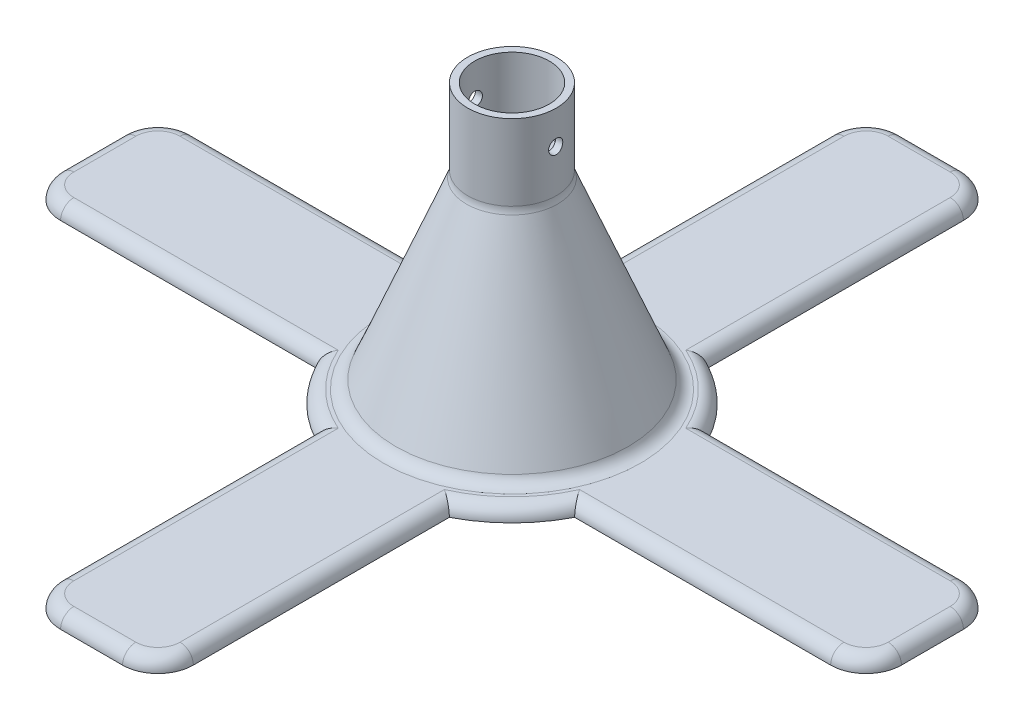
SolidWorks part; units mm, degrees
ref_plane "Front Plane" through (0, 0, 0) normal (0, 0, 1) x (1, 0, 0)
ref_plane "Top Plane" through (0, 0, 0) normal (0, 1, 0) x (1, 0, 0)
ref_plane "Right Plane" through (0, 0, 0) normal (1, 0, 0) x (0, 0, -1)
sketch "Sketch1" plane through (0, 0, 0) normal (0, 1, 0) x (1, 0, 0)
  line L0 (0, 95) -> (0, -95)
  line L1 (0, -55) -> (0, 55) construction
  line L2 (15, -29.159) -> (15, -95)
  line L3 (-95, 0) -> (95, 0)
  line L4 (-55, 0) -> (55, 0) construction
  line L5 (29.159, 15) -> (95, 15)
  line L6 (95, 15) -> (95, 0)
  line L7 (95, -15) -> (29.159, -15)
  line L8 (29.159, -15) -> (95, -15)
  line L9 (95, -15) -> (95, 0)
  line L10 (15, -95) -> (0, -95)
  line L11 (-15, -95) -> (0, -95)
  line L12 (-15, -95) -> (-15, -29.159)
  line L13 (-29.159, -15) -> (-95, -15)
  line L14 (-95, -15) -> (-95, 0)
  line L15 (-95, 15) -> (-95, 0)
  line L16 (-95, 15) -> (-29.159, 15)
  line L17 (-15, 29.159) -> (-15, 95)
  line L18 (-15, 95) -> (0, 95)
  line L19 (15, 95) -> (0, 95)
  line L20 (15, 95) -> (15, 29.159)
  circle A0 centre (0, 0) radius 32.791
  point P6 (0, 0)
  point P12 (0, 0)
  point P35 (0, 0)
  dimension "D3" = 30
  dimension "D1" = 190
  dimension "D2" = 190
  dimension "D4" = 15
  dimension "D5" = 4
extrude "Boss-Extrude1" add sketch "Sketch1" along normal blind 3 contours A0 L3 L6 L5 | A0 L7 L9 L3 | L0 A0 L3 | L3 A0 L0 | L0 A0 L3 | L3 A0 L0 | A0 L0 L18 L17 | A0 L20 L19 L0 | A0 L16 L15 L3 | A0 L3 L14 L13 | A0 L12 L11 L0 | A0 L0 L10 L2 region at (7.5708, 0, -63.2951) region at (-7.5708, 0, -63.2951) region at (13.9169, 0, -13.9169) region at (-13.9169, 0, -13.9169) region at (13.9169, 0, 13.9169) region at (-13.9169, 0, 13.9169) region at (7.5708, 0, 63.2951) region at (-7.5708, 0, 63.2951) region at (-63.2951, 0, 7.5708) region at (-63.2951, 0, -7.5708) region at (63.2951, 0, -7.5708) region at (63.2951, 0, 7.5708)
fillet "Fillet4" radius 8 8 edges at (15, 1.5, 95) (-15, 1.5, 95) (-95, 1.5, 15) (-95, 1.5, -15) (-15, 1.5, -95) (15, 1.5, -95) (95, 1.5, -15) (95, 1.5, 15)
fillet "Fillet5" radius 3 24 edges at (-12.6569, 3, 92.6569) (-15, 3, 58.0795) (-23.1867, 3, 23.1867) (-58.0795, 3, 15) (-92.6569, 3, 12.6569) (-95, 3, 0) (-92.6569, 3, -12.6569) (-58.0795, 3, -15) (-23.1867, 3, -23.1867) (-15, 3, -58.0795) (-12.6569, 3, -92.6569) (0, 3, -95) (12.6569, 3, -92.6569) (15, 3, -58.0795) (23.1867, 3, -23.1867) (58.0795, 3, -15) (92.6569, 3, -12.6569) (95, 3, 0) (92.6569, 3, 12.6569) (58.0795, 3, 15) (23.1867, 3, 23.1867) (15, 3, 58.0795) (12.6569, 3, 92.6569) (0, 3, 95)
sketch "Sketch4" plane through (0, 3, 0) normal (0, 1, 0) x (1, 0, 0)
  circle A0 centre (0, 0) radius 10
extrude "Boss-Extrude4" add sketch "Sketch4" along normal blind 60
chamfer "Chamfer2" distance 17 angle 68 1 edges at (0, 3, 10) first distance on face at (0, 3, 10)
fillet "Fillet7" radius 4 1 edges at (0, 45.0765, 10)
sketch "Sketch5" plane through (0, 0, 0) normal (0, -1, 0) x (1, 0, 0)
  circle A0 centre (0, 0) radius 15
  dimension "D1" = 30
fillet "Fillet8" radius 3 1 edges at (0, 3, 27)
sketch "Sketch6" plane through (0, 63, 0) normal (0, 1, 0) x (1, 0, 0)
  circle A0 centre (0, 0) radius 8.43
extrude "Cut-Extrude2" cut sketch "Sketch6" against normal blind 15
sketch "Sketch8" plane through (0, 0, 0) normal (1, 0, 0) x (0, 0, -1)
  line L0 (0, 63) -> (0, 48)
  line L1 (10, 63) -> (-10, 63) construction
  line L2 (0, 34.7644) -> (0, -34.7644) construction
  line L3 (0, 63) -> (0, 48) construction
  line L4 (0, 55.5) -> (1.6, 55.5)
  circle A0 centre (0, 55.5) radius 1.6
  dimension "D1" = 15
  dimension "D2" = 1.6
extrude "Cut-Extrude3" cut sketch "Sketch8" against normal blind 15 and the other way blind 15 contours L0 A0 | L4 A0 L0 | L0 A0 L4 region at (0, 56.1791, -0.6791) region at (0, 55.5, 0.6791) region at (0, 54.8209, -0.6791)
